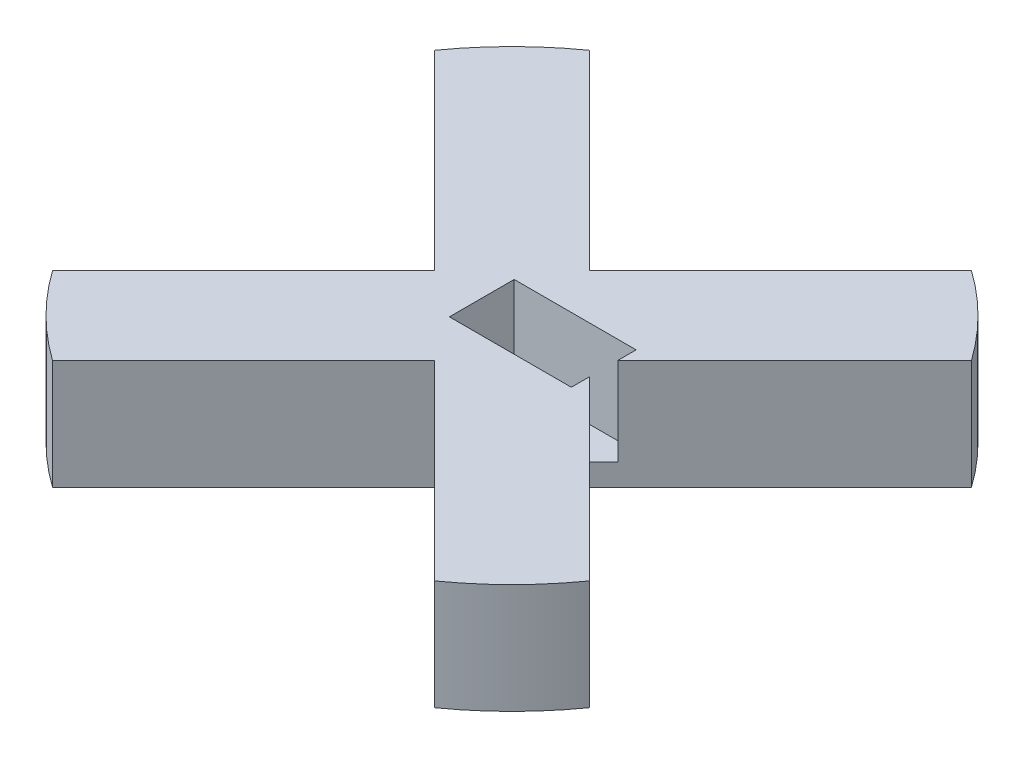
SolidWorks part; units mm, degrees
ref_plane "Front Plane" through (0, 0, 0) normal (0, 0, 1) x (1, 0, 0)
ref_plane "Top Plane" through (0, 0, 0) normal (0, 1, 0) x (1, 0, 0)
ref_plane "Right Plane" through (0, 0, 0) normal (1, 0, 0) x (0, 0, -1)
sketch "Sketch2" plane through (0, 0, 0) normal (0, 1, 0) x (1, 0, 0)
  line L0 (-42.4264, -42.4264) -> (42.4264, 42.4264) construction
  line L1 (14.1421, 0) -> (-14.1421, 0) construction
  line L2 (0, 0) -> (0, 14.1421) construction
  line L3 (14.1421, 0) -> (48.9041, 34.7619)
  line L4 (-42.4264, 42.4264) -> (42.4264, -42.4264) construction
  line L5 (0, -60) -> (0, 60) construction
  line L6 (0, 14.1421) -> (34.7619, 48.9041)
  line L7 (0, -14.1421) -> (34.7619, -48.9041)
  line L8 (0, -14.1421) -> (-34.7619, -48.9041)
  line L9 (0, 14.1421) -> (-34.7619, 48.9041)
  line L10 (-14.1421, 0) -> (-48.9041, -34.7619)
  line L11 (14.1421, 0) -> (48.9041, -34.7619)
  line L12 (-14.1421, 0) -> (-48.9041, 34.7619)
  circle A0 centre (0, 0) radius 60 construction
  arc A1 (-48.9041, 34.7619) -> (-34.7619, 48.9041) centre (0, 0) ccw construction
  arc A2 (-34.7619, 48.9041) -> (-48.9041, 34.7619) centre (0, 0) ccw
  arc A3 (34.7619, 48.9041) -> (48.9041, 34.7619) centre (0, 0) cw
  arc A4 (34.7619, -48.9041) -> (48.9041, -34.7619) centre (0, 0) ccw
  arc A5 (-34.7619, -48.9041) -> (-48.9041, -34.7619) centre (0, 0) cw
  point P9 (0, 0)
  point P12 (0, 0)
  point P15 (0, 0)
  dimension "D1" = 120
  dimension "D2" = 45
  dimension "D3" = 20
  dimension "D4" = 45
  dimension "D5" = 10
extrude "Boss-Extrude2" add sketch "Sketch2" along normal blind 20
sketch "Sketch6" plane through (0, 20, 0) normal (0, 1, 0) x (1, 0, 0)
sketch "Sketch7" plane through (0, 20, 0) normal (0, 1, 0) x (1, 0, 0)
  line L0 (0, 0) -> (5.6, 0) construction
  line L1 (16.7, -5.9) -> (-5.5, -5.9)
  line L2 (16.7, -5.9) -> (16.7, 5.9)
  line L3 (16.7, 5.9) -> (-5.5, 5.9)
  line L4 (-5.5, -5.9) -> (-5.5, 5.9)
  line L5 (16.7, -5.9) -> (-5.5, 5.9) construction
  line L6 (16.7, 5.9) -> (-5.5, -5.9) construction
  point P0 (0, 0)
  dimension "D1" = 5.6
  dimension "D2" = 11.1
  dimension "D3" = 11.8
extrude "Cut-Extrude8" cut sketch "Sketch7" against normal blind 16
